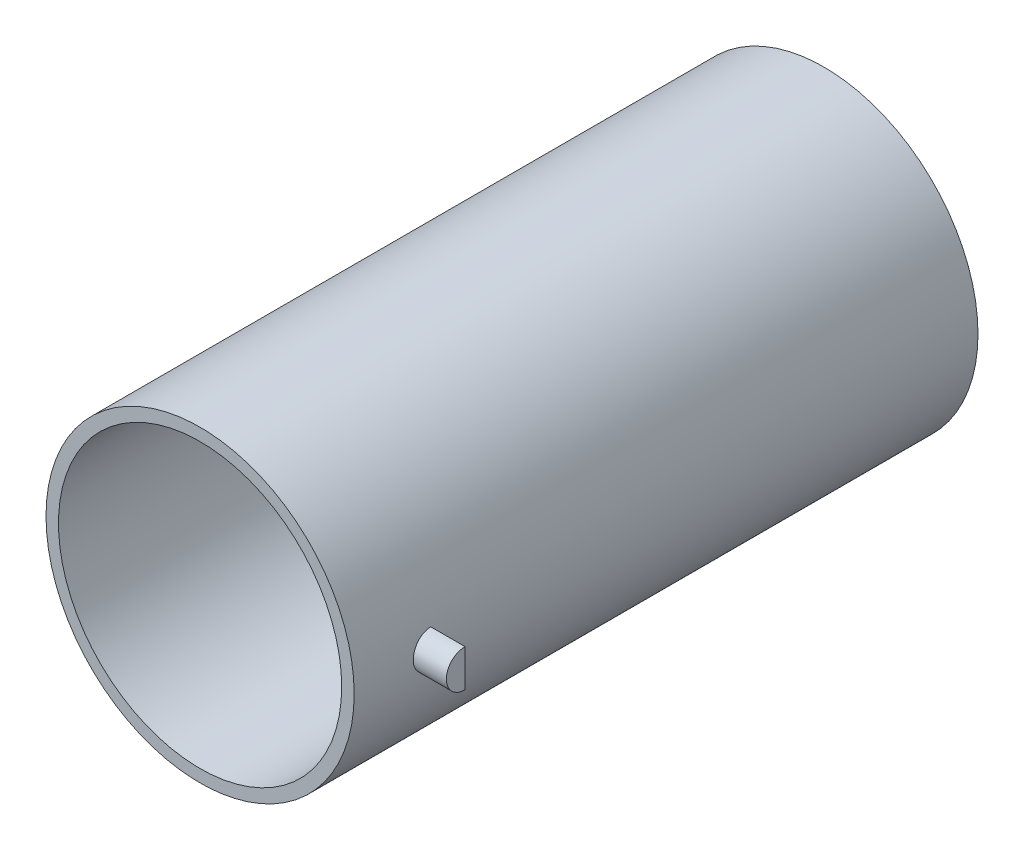
SolidWorks part; units mm, degrees
ref_plane "Front Plane" through (0, 0, 0) normal (0, 0, 1) x (1, 0, 0)
ref_plane "Top Plane" through (0, 0, 0) normal (0, 1, 0) x (1, 0, 0)
ref_plane "Right Plane" through (0, 0, 0) normal (1, 0, 0) x (0, 0, -1)
sketch "Sketch1" plane through (0, 0, 0) normal (0, 0, 1) x (1, 0, 0)
  circle A0 centre (0, 0) radius 31.369
  dimension "D1" = 62.738
extrude "Boss-Extrude1" add sketch "Sketch1" along normal blind 127
sketch "Sketch2" plane through (0, 0, 0) normal (1, 0, 0) x (0, 0, -1)
  line L0 (-111.1616, 3.81) -> (-111.1616, -3.81)
  line L1 (0, 0) -> (-177.7536, 0) construction
  arc A0 (-111.1616, 3.81) -> (-111.1616, -3.81) centre (-111.1616, 0) ccw
  dimension "D1" = 7.62
extrude "Boss-Extrude2" add sketch "Sketch2" against normal blind 38.1 and the other way blind 38.1
shell "Shell3" thickness 2.54 removed face at (31.369, 0, 127)
